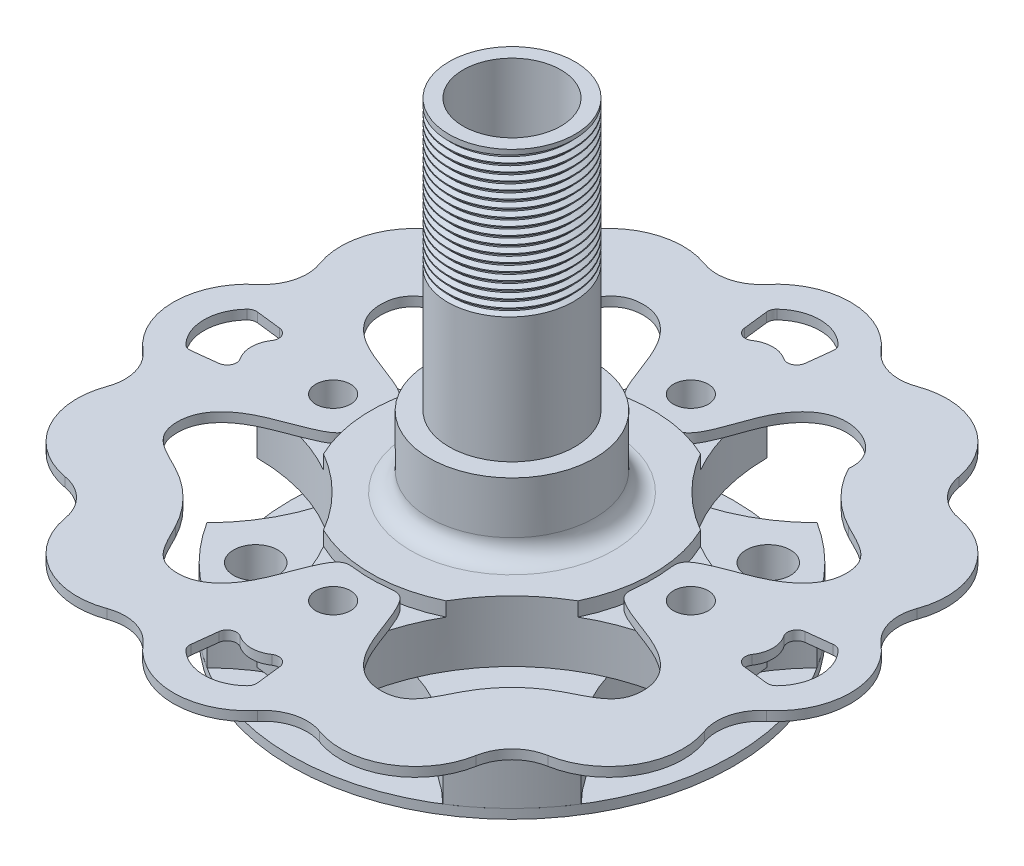
SolidWorks part; units mm, degrees
other "Camera1"
ref_plane "Front Plane" through (0, 0, 0) normal (0, 0, 1) x (1, 0, 0)
ref_plane "Top Plane" through (0, 0, 0) normal (0, 1, 0) x (1, 0, 0)
ref_plane "Right Plane" through (0, 0, 0) normal (1, 0, 0) x (0, 0, -1)
sketch "Sketch1" plane through (0, 0, 0) normal (0, 1, 0) x (1, 0, 0)
  line L0 (-91.3384, 0) -> (0, 0) construction
  line L1 (-79.1014, 45.6692) -> (0, 0) construction
  line L2 (-45.6692, 79.1014) -> (0, 0) construction
  line L3 (0, 91.3384) -> (0, 0) construction
  line L4 (-58.7488, 58.7488) -> (0, 0) construction
  line L5 (-77.6512, 8.9971) -> (-70.888, 8.2135)
  line L9 (0, 91.3384) -> (0, 0) construction
  line L10 (-8.9971, 77.6512) -> (-8.2135, 70.888)
  line L11 (8.9971, 77.6512) -> (8.2135, 70.888)
  line L12 (77.6512, 8.9971) -> (70.888, 8.2135)
  line L13 (0, 91.3384) -> (0, 0) construction
  line L16 (45.6692, 79.1014) -> (0, 0) construction
  line L17 (79.1014, 45.6692) -> (0, 0) construction
  line L18 (91.3384, 0) -> (0, 0) construction
  line L19 (58.7488, 58.7488) -> (0, 0) construction
  line L20 (91.3384, 0) -> (0, 0) construction
  line L23 (0, 91.3384) -> (0, 0) construction
  line L24 (77.6512, -8.9971) -> (70.888, -8.2135)
  line L25 (8.9971, -77.6512) -> (8.2135, -70.888)
  line L26 (-91.3384, 0) -> (0, 0) construction
  line L27 (91.3384, 0) -> (0, 0) construction
  line L28 (77.6512, -8.9971) -> (70.888, -8.2135) [skipped]
  line L30 (-8.9971, -77.6512) -> (-8.2135, -70.888) [skipped]
  line L32 (79.1014, -45.6692) -> (0, 0) construction
  line L33 (45.6692, -79.1014) -> (0, 0) construction
  line L34 (0, -91.3384) -> (0, 0) construction
  line L35 (58.7488, -58.7488) -> (0, 0) construction
  line L36 (0, -91.3384) -> (0, 0) construction
  line L37 (-45.6692, -79.1014) -> (0, 0) construction
  line L38 (-79.1014, -45.6692) -> (0, 0) construction
  line L39 (-58.7488, -58.7488) -> (0, 0) construction
  line L40 (8.9971, 77.6512) -> (8.2135, 70.888) [skipped]
  line L41 (45.6692, 79.1014) -> (0, 0) construction
  line L42 (79.1014, 45.6692) -> (0, 0) construction
  line L43 (58.7488, 58.7488) -> (0, 0) construction
  line L45 (91.3384, 0) -> (0, 0) construction
  line L46 (91.3384, 0) -> (0, 0) construction
  line L47 (79.1014, -45.6692) -> (0, 0) construction
  line L48 (45.6692, -79.1014) -> (0, 0) construction
  line L49 (0, -91.3384) -> (0, 0) construction
  line L50 (58.7488, -58.7488) -> (0, 0) construction
  line L51 (0, -91.3384) -> (0, 0) construction
  line L52 (91.3384, 0) -> (0, 0) construction
  line L53 (-8.9971, -77.6512) -> (-8.2135, -70.888)
  line L54 (-77.6512, -8.9971) -> (-70.888, -8.2135)
  line L55 (0, -91.3384) -> (0, 0) construction
  line L56 (-45.6692, -79.1014) -> (0, 0) construction
  line L57 (-79.1014, -45.6692) -> (0, 0) construction
  line L58 (-91.3384, 0) -> (0, 0) construction
  line L59 (-58.7488, -58.7488) -> (0, 0) construction
  line L60 (-91.3384, 0) -> (0, 0) construction
  line L61 (0, -91.3384) -> (0, 0) construction
  arc A0 (-83.0834, 0) -> (0, 83.0834) centre (0, 0) cw construction
  arc A2 (-91.3384, 0) -> (-84.1072, 15.4663) centre (-71.1829, 0) cw
  arc A3 (-84.1072, 15.4663) -> (-80.5721, 28.6594) centre (-91.7199, 24.5763) ccw
  arc A4 (-80.5721, 28.6594) -> (-65.1058, 55.4478) centre (-61.6462, 35.5915) cw
  arc A5 (-65.1058, 55.4478) -> (-55.4478, 65.1058) centre (-67.1436, 67.1436) ccw
  arc A6 (-55.4478, 65.1058) -> (-28.6594, 80.5721) centre (-35.5915, 61.6462) cw
  arc A7 (-28.6594, 80.5721) -> (-15.4663, 84.1072) centre (-24.5763, 91.7199) ccw
  arc A8 (-15.4663, 84.1072) -> (0, 91.3384) centre (0, 71.1829) cw
  arc A9 (-61.618, 35.4294) -> (-35.4294, 61.618) centre (-67.1436, 67.1436) ccw
  arc A10 (-38.1, 0) -> (-37.7962, 4.8015) centre (0, 0) cw
  arc A11 (-83.0834, 0) -> (-79.7781, 8.2307) centre (-71.1829, 0) cw
  arc A12 (-69.0761, 4.2678) -> (-70.3834, 0) centre (-62.7634, 0) ccw
  arc A14 (-83.0834, 0) -> (-78.8139, 9.1318) centre (-71.1829, 0) cw construction
  arc A15 (-77.6512, 8.9971) -> (-79.7781, 8.2307) centre (-77.9435, 6.474) ccw
  arc A16 (-69.0761, 4.2678) -> (-70.888, 8.2135) centre (-71.1804, 5.6904) ccw
  circle A17 centre (-48.26, 0) radius 4.699
  arc A29 (0, 38.1) -> (-4.8015, 37.7962) centre (0, 0) ccw
  arc A30 (-4.2678, 69.0761) -> (0, 70.3834) centre (0, 62.7634) cw
  arc A36 (-4.2678, 69.0761) -> (-8.2135, 70.888) centre (-5.6904, 71.1804) cw
  arc A41 (-8.9971, 77.6512) -> (-8.2307, 79.7781) centre (-6.474, 77.9435) cw
  arc A42 (0, 83.0834) -> (-8.2307, 79.7781) centre (0, 71.1829) ccw
  arc A50 (0, 91.3384) -> (15.4663, 84.1072) centre (0, 71.1829) cw
  arc A51 (15.4663, 84.1072) -> (28.6594, 80.5721) centre (24.5763, 91.7199) ccw
  arc A57 (28.6594, 80.5721) -> (55.4478, 65.1058) centre (35.5915, 61.6462) cw
  arc A62 (55.4478, 65.1058) -> (65.1058, 55.4478) centre (67.1436, 67.1436) ccw
  arc A63 (65.1058, 55.4478) -> (80.5721, 28.6594) centre (61.6462, 35.5915) cw
  arc A71 (80.5721, 28.6594) -> (84.1072, 15.4663) centre (91.7199, 24.5763) ccw
  arc A72 (84.1072, 15.4663) -> (91.3384, 0) centre (71.1829, 0) cw
  arc A78 (-38.1, 0) -> (-37.7962, -4.8015) centre (0, 0) ccw
  arc A81 (-69.0761, -4.2678) -> (-70.3834, 0) centre (-62.7634, 0) cw
  arc A83 (35.4294, 61.618) -> (61.618, 35.4294) centre (67.1436, 67.1436) ccw
  arc A84 (0, 38.1) -> (4.8015, 37.7962) centre (0, 0) cw
  arc A85 (91.3384, 0) -> (84.1072, -15.4663) centre (71.1829, 0) cw [skipped]
  arc A86 (84.1072, -15.4663) -> (80.5721, -28.6594) centre (91.7199, -24.5763) ccw [skipped]
  arc A87 (80.5721, -28.6594) -> (65.1058, -55.4478) centre (61.6462, -35.5915) cw [skipped]
  arc A88 (65.1058, -55.4478) -> (55.4478, -65.1058) centre (67.1436, -67.1436) ccw [skipped]
  arc A89 (55.4478, -65.1058) -> (28.6594, -80.5721) centre (35.5915, -61.6462) cw [skipped]
  arc A90 (28.6594, -80.5721) -> (15.4663, -84.1072) centre (24.5763, -91.7199) ccw [skipped]
  arc A91 (15.4663, -84.1072) -> (0, -91.3384) centre (0, -71.1829) cw [skipped]
  arc A92 (61.618, -35.4294) -> (35.4294, -61.618) centre (67.1436, -67.1436) ccw [skipped]
  arc A93 (83.0834, 0) -> (79.7781, -8.2307) centre (71.1829, 0) cw [skipped]
  arc A95 (77.6512, -8.9971) -> (79.7781, -8.2307) centre (77.9435, -6.474) ccw [skipped]
  arc A96 (69.0761, -4.2678) -> (70.888, -8.2135) centre (71.1804, -5.6904) ccw [skipped]
  arc A102 (0, -91.3384) -> (-15.4663, -84.1072) centre (0, -71.1829) cw [skipped]
  arc A103 (-15.4663, -84.1072) -> (-28.6594, -80.5721) centre (-24.5763, -91.7199) ccw [skipped]
  arc A104 (-28.6594, -80.5721) -> (-55.4478, -65.1058) centre (-35.5915, -61.6462) cw [skipped]
  arc A105 (-55.4478, -65.1058) -> (-65.1058, -55.4478) centre (-67.1436, -67.1436) ccw [skipped]
  arc A106 (-65.1058, -55.4478) -> (-80.5721, -28.6594) centre (-61.6462, -35.5915) cw [skipped]
  arc A107 (-80.5721, -28.6594) -> (-84.1072, -15.4663) centre (-91.7199, -24.5763) ccw [skipped]
  arc A108 (-84.1072, -15.4663) -> (-91.3384, 0) centre (-71.1829, 0) cw [skipped]
  arc A109 (-35.4294, -61.618) -> (-61.618, -35.4294) centre (-67.1436, -67.1436) ccw [skipped]
  arc A110 (0, -38.1) -> (-4.8015, -37.7962) centre (0, 0) cw [skipped]
  arc A111 (0, -83.0834) -> (-8.2307, -79.7781) centre (0, -71.1829) cw [skipped]
  arc A112 (-4.2678, -69.0761) -> (0, -70.3834) centre (0, -62.7634) ccw [skipped]
  arc A114 (-8.9971, -77.6512) -> (-8.2307, -79.7781) centre (-6.474, -77.9435) ccw [skipped]
  arc A115 (-4.2678, -69.0761) -> (-8.2135, -70.888) centre (-5.6904, -71.1804) ccw [skipped]
  arc A119 (83.0834, 0) -> (0, -83.0834) centre (0, 0) cw construction
  arc A121 (0, -83.0834) -> (-83.0834, 0) centre (0, 0) cw construction
  arc A123 (0, 91.3384) -> (15.4663, 84.1072) centre (0, 71.1829) cw [skipped]
  arc A124 (15.4663, 84.1072) -> (28.6594, 80.5721) centre (24.5763, 91.7199) ccw [skipped]
  arc A125 (28.6594, 80.5721) -> (55.4478, 65.1058) centre (35.5915, 61.6462) cw [skipped]
  arc A126 (55.4478, 65.1058) -> (65.1058, 55.4478) centre (67.1436, 67.1436) ccw [skipped]
  arc A127 (65.1058, 55.4478) -> (80.5721, 28.6594) centre (61.6462, 35.5915) cw [skipped]
  arc A128 (80.5721, 28.6594) -> (84.1072, 15.4663) centre (91.7199, 24.5763) ccw [skipped]
  arc A129 (84.1072, 15.4663) -> (91.3384, 0) centre (71.1829, 0) cw [skipped]
  arc A130 (35.4294, 61.618) -> (61.618, 35.4294) centre (67.1436, 67.1436) ccw [skipped]
  arc A131 (0, 38.1) -> (4.8015, 37.7962) centre (0, 0) cw [skipped]
  arc A132 (0, 83.0834) -> (8.2307, 79.7781) centre (0, 71.1829) cw [skipped]
  arc A133 (4.2678, 69.0761) -> (0, 70.3834) centre (0, 62.7634) ccw [skipped]
  arc A135 (8.9971, 77.6512) -> (8.2307, 79.7781) centre (6.474, 77.9435) ccw [skipped]
  arc A136 (4.2678, 69.0761) -> (8.2135, 70.888) centre (5.6904, 71.1804) ccw [skipped]
  arc A138 (0, 83.0834) -> (83.0834, 0) centre (0, 0) cw construction
  arc A144 (38.1, 0) -> (37.7962, -4.8015) centre (0, 0) cw [skipped]
  arc A145 (69.0761, -4.2678) -> (70.3834, 0) centre (62.7634, 0) ccw [skipped]
  arc A146 (0, 83.0834) -> (8.2307, 79.7781) centre (0, 71.1829) cw
  arc A147 (4.2678, 69.0761) -> (0, 70.3834) centre (0, 62.7634) ccw
  arc A148 (8.9971, 77.6512) -> (8.2307, 79.7781) centre (6.474, 77.9435) ccw
  arc A149 (4.2678, 69.0761) -> (8.2135, 70.888) centre (5.6904, 71.1804) ccw
  circle A150 centre (0, 48.26) radius 4.699
  arc A151 (38.1, 0) -> (37.7962, 4.8015) centre (0, 0) ccw
  arc A152 (69.0761, 4.2678) -> (70.3834, 0) centre (62.7634, 0) cw
  arc A153 (69.0761, 4.2678) -> (70.888, 8.2135) centre (71.1804, 5.6904) cw
  arc A154 (77.6512, 8.9971) -> (79.7781, 8.2307) centre (77.9435, 6.474) cw
  arc A155 (83.0834, 0) -> (79.7781, 8.2307) centre (71.1829, 0) ccw
  arc A156 (0, 38.1) -> (-4.8015, 37.7962) centre (0, 0) ccw
  arc A157 (-4.2678, 69.0761) -> (0, 70.3834) centre (0, 62.7634) cw
  arc A158 (0, 83.0834) -> (83.0834, 0) centre (0, 0) cw construction
  arc A159 (0, 91.3384) -> (91.3384, 0) centre (0, 0) cw construction
  arc A160 (91.3384, 0) -> (84.1072, -15.4663) centre (71.1829, 0) cw
  arc A161 (84.1072, -15.4663) -> (80.5721, -28.6594) centre (91.7199, -24.5763) ccw
  arc A162 (80.5721, -28.6594) -> (65.1058, -55.4478) centre (61.6462, -35.5915) cw
  arc A163 (65.1058, -55.4478) -> (55.4478, -65.1058) centre (67.1436, -67.1436) ccw
  arc A164 (55.4478, -65.1058) -> (28.6594, -80.5721) centre (35.5915, -61.6462) cw
  arc A165 (28.6594, -80.5721) -> (15.4663, -84.1072) centre (24.5763, -91.7199) ccw
  arc A166 (15.4663, -84.1072) -> (0, -91.3384) centre (0, -71.1829) cw
  arc A167 (61.618, -35.4294) -> (35.4294, -61.618) centre (67.1436, -67.1436) ccw
  arc A168 (38.1, 0) -> (37.7962, -4.8015) centre (0, 0) cw
  arc A169 (83.0834, 0) -> (79.7781, -8.2307) centre (71.1829, 0) cw
  arc A170 (69.0761, -4.2678) -> (70.3834, 0) centre (62.7634, 0) ccw
  arc A171 (77.6512, -8.9971) -> (79.7781, -8.2307) centre (77.9435, -6.474) ccw
  arc A172 (69.0761, -4.2678) -> (70.888, -8.2135) centre (71.1804, -5.6904) ccw
  circle A173 centre (48.26, 0) radius 4.699
  arc A174 (0, -38.1) -> (4.8015, -37.7962) centre (0, 0) ccw
  arc A175 (4.2678, -69.0761) -> (0, -70.3834) centre (0, -62.7634) cw
  arc A176 (4.2678, -69.0761) -> (8.2135, -70.888) centre (5.6904, -71.1804) cw
  arc A177 (8.9971, -77.6512) -> (8.2307, -79.7781) centre (6.474, -77.9435) cw
  arc A178 (0, -83.0834) -> (8.2307, -79.7781) centre (0, -71.1829) ccw
  arc A179 (38.1, 0) -> (37.7962, 4.8015) centre (0, 0) ccw
  arc A180 (69.0761, 4.2678) -> (70.3834, 0) centre (62.7634, 0) cw
  arc A181 (83.0834, 0) -> (0, -83.0834) centre (0, 0) cw construction
  arc A182 (91.3384, 0) -> (0, -91.3384) centre (0, 0) cw construction
  arc A183 (0, -91.3384) -> (-15.4663, -84.1072) centre (0, -71.1829) cw
  arc A184 (-15.4663, -84.1072) -> (-28.6594, -80.5721) centre (-24.5763, -91.7199) ccw
  arc A185 (-28.6594, -80.5721) -> (-55.4478, -65.1058) centre (-35.5915, -61.6462) cw
  arc A186 (-55.4478, -65.1058) -> (-65.1058, -55.4478) centre (-67.1436, -67.1436) ccw
  arc A187 (-65.1058, -55.4478) -> (-80.5721, -28.6594) centre (-61.6462, -35.5915) cw
  arc A188 (-80.5721, -28.6594) -> (-84.1072, -15.4663) centre (-91.7199, -24.5763) ccw
  arc A189 (-84.1072, -15.4663) -> (-91.3384, 0) centre (-71.1829, 0) cw
  arc A190 (-35.4294, -61.618) -> (-61.618, -35.4294) centre (-67.1436, -67.1436) ccw
  arc A191 (0, -38.1) -> (-4.8015, -37.7962) centre (0, 0) cw
  arc A192 (0, -83.0834) -> (-8.2307, -79.7781) centre (0, -71.1829) cw
  arc A193 (-4.2678, -69.0761) -> (0, -70.3834) centre (0, -62.7634) ccw
  arc A194 (-8.9971, -77.6512) -> (-8.2307, -79.7781) centre (-6.474, -77.9435) ccw
  arc A195 (-4.2678, -69.0761) -> (-8.2135, -70.888) centre (-5.6904, -71.1804) ccw
  circle A196 centre (0, -48.26) radius 4.699
  arc A197 (-38.1, 0) -> (-37.7962, -4.8015) centre (0, 0) ccw
  arc A198 (-69.0761, -4.2678) -> (-70.3834, 0) centre (-62.7634, 0) cw
  arc A199 (-69.0761, -4.2678) -> (-70.888, -8.2135) centre (-71.1804, -5.6904) cw
  arc A200 (-77.6512, -8.9971) -> (-79.7781, -8.2307) centre (-77.9435, -6.474) cw
  arc A201 (-83.0834, 0) -> (-79.7781, -8.2307) centre (-71.1829, 0) ccw
  arc A202 (0, -38.1) -> (4.8015, -37.7962) centre (0, 0) ccw
  arc A203 (4.2678, -69.0761) -> (0, -70.3834) centre (0, -62.7634) cw
  arc A204 (0, -83.0834) -> (-83.0834, 0) centre (0, 0) cw construction
  arc A205 (0, -91.3384) -> (-91.3384, 0) centre (0, 0) cw construction
  spline S0 degree 3 poles (-52.2384, 38.6101) (-57.1023, 36.0693) (-62.2546, 34.2055) (-63.3566, 23.0387) (-56.4818, 14.6017) (-38.7119, 10.4134) (-37.5569, 6.6856) (-37.7962, 4.8015) knots 0 0 0 0 0.284167 0.347787 0.6362 0.911955 1 1 1 1
  spline S1 degree 3 poles (-38.6101, 52.2384) (-36.0693, 57.1023) (-34.2055, 62.2546) (-23.0387, 63.3566) (-14.6017, 56.4818) (-10.4134, 38.7119) (-6.6856, 37.5569) (-4.8015, 37.7962) knots 0 0 0 0 0.284167 0.347787 0.6362 0.911955 1 1 1 1
  spline S2 degree 3 poles (38.6101, 52.2384) (39.4918, 58.7472) (27.2418, 66.5399) (13.0177, 55.4204) (10.7787, 36.3141) (4.8015, 37.7962) knots 0 0 0 0 0.347787 0.6362 1 1 1 1
  spline S3 degree 3 poles (52.2384, 38.6101) (57.1023, 36.0693) (62.2546, 34.2055) (63.3566, 23.0387) (56.4818, 14.6017) (38.7119, 10.4134) (37.5569, 6.6856) (37.7962, 4.8015) knots 0 0 0 0 0.284167 0.347787 0.6362 0.911955 1 1 1 1
  spline S4 degree 3 poles (52.2384, -38.6101) (57.1023, -36.0693) (62.2546, -34.2055) (63.3566, -23.0387) (56.4818, -14.6017) (38.7119, -10.4134) (37.5569, -6.6856) (37.7962, -4.8015) knots 0 0 0 0 0.284167 0.347787 0.6362 0.911955 1 1 1 1
  spline S5 degree 3 poles (38.6101, -52.2384) (36.0693, -57.1023) (34.2055, -62.2546) (23.0387, -63.3566) (14.6017, -56.4818) (10.4134, -38.7119) (6.6856, -37.5569) (4.8015, -37.7962) knots 0 0 0 0 0.284167 0.347787 0.6362 0.911955 1 1 1 1
  spline S6 degree 3 poles (-38.6101, -52.2384) (-36.0693, -57.1023) (-34.2055, -62.2546) (-23.0387, -63.3566) (-14.6017, -56.4818) (-10.4134, -38.7119) (-6.6856, -37.5569) (-4.8015, -37.7962) knots 0 0 0 0 0.284167 0.347787 0.6362 0.911955 1 1 1 1
  spline S7 degree 3 poles (-52.2384, -38.6101) (-57.1023, -36.0693) (-62.2546, -34.2055) (-63.3566, -23.0387) (-56.4818, -14.6017) (-38.7119, -10.4134) (-37.5569, -6.6856) (-37.7962, -4.8015) knots 0 0 0 0 0.284167 0.347787 0.6362 0.911955 1 1 1 1
  point P26 (0, 0)
  point P27 (-79.1014, 45.6692)
  point P32 (-45.6692, 79.1014)
  point P89 (0, 0)
  point P90 (0, 0)
  point P124 (0, 0)
  point P125 (0, 0)
  point P127 (0, 0)
  point P131 (0, 0)
  point P146 (0, 0)
  point P156 (0, 0)
  point P190 (0, 0)
  point P191 (0, 0)
  point P193 (0, 0)
  point P197 (0, 0)
  point P203 (0, 0)
  point P223 (0, 0)
  point P237 (0, 0)
  point P454 (0, 0)
  point P456 (0, 0)
  point P458 (0, 0)
  point P462 (0, 0)
  point P463 (0, 0)
  dimension "D5" = 10.16
  dimension "D8" = 7.62
  dimension "D11" = 2.54
  dimension "D12" = 2.54
  dimension "D3" = 9.398
  dimension "D7" = 4
  dimension "D4" = 20.32
  dimension "D6" = 8.255
  dimension "D13" = 4
extrude "Boss-Extrude2" add sketch "Sketch1" along normal blind 2.54 contours L10 A8 A7 A6 A5 A4 A3 A2 A11 A15 L5 A16 A12 A81 region at (-87.101, 0, -7.4424)
sketch "Sketch4" plane through (0, 0, 0) normal (0, -1, 0) x (1, 0, 0)
  line L0 (-58.858, 9.9314) -> (-58.858, -9.9314) construction
  line L1 (9.9314, 58.858) -> (-9.9314, 58.858) construction
  line L2 (58.858, -9.9314) -> (58.858, 9.9314) construction
  line L3 (-9.9314, -58.858) -> (9.9314, -58.858) construction
  line L4 (-9.9314, 58.858) -> (-58.858, 58.858) construction
  line L5 (-58.858, 58.858) -> (-58.858, 9.9314) construction
  circle A0 centre (0, 0) radius 59.69
  circle A1 centre (0, 0) radius 38.1 construction
  arc A2 (58.858, 9.9314) -> (9.9314, 58.858) centre (58.858, 58.858) cw
  arc A3 (9.9314, -58.858) -> (58.858, -9.9314) centre (58.858, -58.858) cw
  arc A5 (-9.9314, 58.858) -> (-58.858, 9.9314) centre (-58.858, 58.858) cw
  arc A6 (-58.858, -9.9314) -> (-9.9314, -58.858) centre (-58.858, -58.858) cw
  circle A15 centre (48.26, 0) radius 4.699 construction
  circle A16 centre (0, -48.26) radius 4.699 construction
  circle A17 centre (-48.26, 0) radius 4.699 construction
  circle A18 centre (0, 48.26) radius 4.699 construction
  circle A19 centre (48.26, 0) radius 4.699
  circle A20 centre (0, -48.26) radius 4.699
  circle A21 centre (-48.26, 0) radius 4.699
  circle A22 centre (0, 48.26) radius 4.699
  point P9 (-58.858, 0)
  point P12 (0, 58.858)
  point P19 (0, 0)
  point P31 (0, 0)
  dimension "D1" = 119.38
  dimension "D2" = 19.8628
  dimension "D4" = 90
  dimension "D3" = 4
  dimension "D5" = 4
extrude "Boss-Extrude3" add sketch "Sketch4" along normal blind 12.7 contours A0 A6 A3 A2 A5 A22 A21 A20 A19 region at (0, 0, 0)
sketch "Sketch5" plane through (0, -12.7, 0) normal (0, -1, 0) x (1, 0, 0)
  circle A4 centre (34.574, -34.574) radius 5.969
  circle A5 centre (34.574, 34.574) radius 5.969
  circle A6 centre (-34.574, 34.574) radius 5.969
  circle A7 centre (-34.574, -34.574) radius 5.969
  arc A16 (-50.5004, -31.8215) -> (-31.8215, -50.5004) centre (0, 0) ccw
  arc A17 (31.8215, -50.5004) -> (-31.8215, -50.5004) centre (0, -82.3219) ccw
  arc A18 (31.8215, -50.5004) -> (50.5004, -31.8215) centre (0, 0) ccw
  arc A19 (50.5004, 31.8215) -> (50.5004, -31.8215) centre (82.3219, 0) ccw
  arc A20 (50.5004, 31.8215) -> (31.8215, 50.5004) centre (0, 0) ccw
  arc A21 (-31.8215, 50.5004) -> (31.8215, 50.5004) centre (0, 82.3219) ccw
  arc A22 (-31.8215, 50.5004) -> (-50.5004, 31.8215) centre (0, 0) ccw
  arc A23 (-50.5004, -31.8215) -> (-50.5004, 31.8215) centre (-82.3219, 0) ccw
extrude "Boss-Extrude4" add sketch "Sketch5" along normal blind 15.24 separate body
sketch "Sketch6" plane through (0, -27.94, 0) normal (0, -1, 0) x (1, 0, 0)
  circle A0 centre (0, 0) radius 59.69
  circle A1 centre (0, 0) radius 25.4
  arc A2 (58.858, -9.9314) -> (58.858, 9.9314) centre (0, 0) ccw construction
  circle A3 centre (-34.574, -34.574) radius 5.969 construction
  circle A4 centre (34.574, -34.574) radius 5.969 construction
  circle A5 centre (34.574, 34.574) radius 5.969 construction
  circle A6 centre (-34.574, 34.574) radius 5.969 construction
  circle A7 centre (-34.574, -34.574) radius 5.969
  circle A8 centre (34.574, -34.574) radius 5.969
  circle A9 centre (34.574, 34.574) radius 5.969
  circle A10 centre (-34.574, 34.574) radius 5.969
  dimension "D1" = 50.8
extrude "Boss-Extrude5" add sketch "Sketch6" along normal blind 2.54 separate body
sketch "Sketch7" plane through (0, 0, 0) normal (0, 1, 0) x (1, 0, 0)
  circle A0 centre (0, 0) radius 38.1
  arc A1 (-37.7962, 4.8015) -> (-37.7962, -4.8015) centre (0, 0) ccw construction
  arc A11 (-45.2034, 11.8754) -> (-11.8754, 45.2034) centre (-58.858, 58.858) ccw
  arc A12 (-37.7962, 4.8015) -> (-37.7962, -4.8015) centre (0, 0) ccw
  arc A13 (-11.8754, -45.2034) -> (-45.2034, -11.8754) centre (-58.858, -58.858) ccw
  arc A15 (45.2034, -11.8754) -> (11.8754, -45.2034) centre (58.858, -58.858) ccw
  arc A17 (11.9707, 44.8798) -> (45.2034, 11.8754) centre (58.858, 58.858) ccw
  arc A19 (-34.3305, 16.5234) -> (-16.5234, 34.3305) centre (-58.858, 58.858) ccw
  arc A20 (-37.7962, 4.8015) -> (-37.7962, -4.8015) centre (0, 0) ccw
  arc A21 (-16.5234, -34.3305) -> (-34.3305, -16.5234) centre (-58.858, -58.858) ccw
  arc A23 (34.3305, -16.5234) -> (16.5234, -34.3305) centre (58.858, -58.858) ccw
  arc A25 (16.5234, 34.3305) -> (34.3305, 16.5234) centre (58.858, 58.858) ccw
  arc A26 (4.8015, 37.7962) -> (-4.8015, 37.7962) centre (0, 0) ccw
  arc A27 (4.8015, 37.7962) -> (-4.8015, 37.7962) centre (0, 0) ccw
  arc A28 (-4.8015, -37.7962) -> (4.8015, -37.7962) centre (0, 0) ccw
  arc A29 (-4.8015, -37.7962) -> (4.8015, -37.7962) centre (0, 0) ccw
  arc A30 (37.7962, -4.8015) -> (37.7962, 4.8015) centre (0, 0) ccw
  arc A31 (37.7962, -4.8015) -> (37.7962, 4.8015) centre (0, 0) ccw
  spline S8 degree 3 poles (2976.9947, 358.0163) (33.5756, 126.9835) (-48.0553, -146.4387) (2.9292, 414.707) (-862.0018, -2830.3277) knots -0.437178 -0.437178 -0.437178 -0.437178 0.862417 3.114377 3.114377 3.114377 3.114377 only from (-4.8015, 37.7962) to (-11.8754, 45.2034)
  spline S9 degree 3 poles (900.8755, 335.8111) (-245.803, 10.7239) (51.6226, 30.7541) (-75.4367, -16.6676) (-179.4615, -985.0902) knots -0.726756 -0.726756 -0.726756 -0.726756 0.911955 1.806148 1.806148 1.806148 1.806148 only from (-45.2034, 11.8754) to (-37.7962, 4.8015)
  spline S10 degree 3 poles (-4.8015, 37.7962) (-6.6856, 37.5569) (-8.9976, 38.2732) (-10.7743, 42.3579) (-11.8754, 45.2034) knots 0.774372 0.774372 0.774372 0.774372 0.862417 1 1 1 1
  spline S11 degree 3 poles (-358.0163, 2976.9947) (-126.9835, 33.5756) (146.4387, -48.0553) (-414.707, 2.9292) (2830.3277, -862.0018) knots -0.437178 -0.437178 -0.437178 -0.437178 0.862417 3.114377 3.114377 3.114377 3.114377 only from (-37.7962, -4.8015) to (-45.2034, -11.8754)
  spline S12 degree 3 poles (-37.7962, -4.8015) (-37.5569, -6.6856) (-38.2732, -8.9976) (-42.3579, -10.7743) (-45.2034, -11.8754) knots 0.774372 0.774372 0.774372 0.774372 0.862417 1 1 1 1
  spline S13 degree 3 poles (-862.0004, 2830.3225) (2.9291, -414.7066) (-48.055, 146.4363) (33.5749, -126.9812) (2976.8937, -358.0084) knots -1.340004 -1.340004 -1.340004 -1.340004 0.911955 2.211535 2.211535 2.211535 2.211535 only from (-11.8754, -45.2034) to (-4.8015, -37.7962)
  spline S14 degree 3 poles (-11.8754, -45.2034) (-10.7743, -42.3579) (-8.9976, -38.2732) (-6.6856, -37.5569) (-4.8015, -37.7962) knots 0.774372 0.774372 0.774372 0.774372 0.911955 1 1 1 1
  spline S15 degree 3 poles (-2976.9947, -358.0163) (-33.5756, -126.9835) (48.0553, 146.4387) (-2.9292, -414.707) (862.0018, 2830.3277) knots -0.437178 -0.437178 -0.437178 -0.437178 0.862417 3.114377 3.114377 3.114377 3.114377 only from (4.8015, -37.7962) to (11.8754, -45.2034)
  spline S16 degree 3 poles (4.8015, -37.7962) (6.6856, -37.5569) (8.9976, -38.2732) (10.7743, -42.3579) (11.8754, -45.2034) knots 0.774372 0.774372 0.774372 0.774372 0.862417 1 1 1 1
  spline S17 degree 3 poles (-2830.3225, -862.0004) (414.7066, 2.9291) (-146.4363, -48.055) (126.9812, 33.5749) (358.0084, 2976.8937) knots -1.340004 -1.340004 -1.340004 -1.340004 0.911955 2.211535 2.211535 2.211535 2.211535 only from (45.2034, -11.8754) to (37.7962, -4.8015)
  spline S18 degree 3 poles (45.2034, -11.8754) (42.3579, -10.7743) (38.2732, -8.9976) (37.5569, -6.6856) (37.7962, -4.8015) knots 0.774372 0.774372 0.774372 0.774372 0.911955 1 1 1 1
  spline S19 degree 3 poles (358.0163, -2976.9947) (126.9835, -33.5756) (-146.4387, 48.0553) (414.707, -2.9292) (-2830.3277, 862.0018) knots -0.437178 -0.437178 -0.437178 -0.437178 0.862417 3.114377 3.114377 3.114377 3.114377 only from (37.7962, 4.8015) to (45.2034, 11.8754)
  spline S20 degree 3 poles (37.7962, 4.8015) (37.5569, 6.6856) (38.2732, 8.9976) (42.3579, 10.7743) (45.2034, 11.8754) knots 0.774372 0.774372 0.774372 0.774372 0.862417 1 1 1 1
  spline S21 degree 3 poles (1348.0294, -2639.3043) (-1227.4206, 2924.7866) (1222.4599, -2840.1968) (-1227.3035, 2772.6078) knots -1.32616 -1.32616 -1.32616 -1.32616 2.776909 2.776909 2.776909 2.776909 only from (11.9707, 44.8798) to (4.8015, 37.7962)
  spline S22 degree 3 poles (11.9707, 44.8798) (10.2888, 40.4191) (8.4039, 36.903) (4.8015, 37.7962) knots 0.780744 0.780744 0.780744 0.780744 1 1 1 1
  arc M20 (-11.8754, 45.2034) -> (-45.2034, 11.8754) centre (-58.858, 58.858) cw
  arc M22 (-37.7962, 4.8015) -> (-37.7962, -4.8015) centre (0, 0) ccw
  arc M24 (-45.2034, -11.8754) -> (-11.8754, -45.2034) centre (-58.858, -58.858) cw
  arc M28 (11.8754, -45.2034) -> (45.2034, -11.8754) centre (58.858, -58.858) cw
  arc M32 (45.2034, 11.8754) -> (11.9707, 44.8798) centre (58.858, 58.858) cw
  dimension "D1" = 0
extrude "Boss-Extrude7" add sketch "Sketch7" along normal blind 3.81 contours A0 M28 M32 M20 M22 M24 region at (0, 0, 0.0002)
sketch "Sketch8" plane through (0, 3.81, 0) normal (0, 1, 0) x (1, 0, 0)
  circle A0 centre (0, 0) radius 22.3012
  dimension "D1" = 44.6024
extrude "Boss-Extrude8" add sketch "Sketch8" along normal blind 19.05
sketch "Sketch9" plane through (0, 22.86, 0) normal (0, 1, 0) x (1, 0, 0)
  circle A0 centre (0, 0) radius 16.9926
  dimension "D1" = 33.9852
extrude "Boss-Extrude9" add sketch "Sketch9" along normal blind 73.025 separate body
sketch "Sketch10" plane through (0, 95.885, 0) normal (0, 1, 0) x (1, 0, 0)
  circle A2 centre (0, 0) radius 13.1826
  circle A3 centre (0, 0) radius 13.1826
  dimension "D1" = 3.81
extrude "Cut-Extrude1" cut sketch "Sketch10" against normal through all both and the other way through all
thread "Thread1" pitch 2.1167 method cut profile "Thread Profile1" start angle 0, offset 0, length 38.1, pitch 2.1167, diameter 33.9852
ref_plane "Plane1" through (-16.9926, 95.885, 0) normal (0, 0, 1) x (-1, 0, 0)
sketch "Thread Profile1" plane through (-16.9926, 95.885, 0) normal (0, 0, 1) x (-1, 0, 0)
  line L0 (0, 0) -> (0, 2.1167) construction
  line L11 (0, 0) -> (0, 1.8521)
  line L12 (0, 1.8521) -> (-1.1457, 1.1906)
  line L13 (-1.1457, 1.1906) -> (-1.1457, 0.6615)
  line L15 (-1.1457, 0.6615) -> (0, 0)
  line L17 (-1.1457, 0.926) -> (0, 0.926) construction
  point P2 (0, 0)
  dimension "Pitch" = 2.1167
  dimension "Profile_Angle" = 60
  dimension "Profile_Land" = 0.5292
  dimension "Profile_Height" = 1.1457
fillet "Fillet2" radius 5.08 1 edges at (0, 3.81, 22.3012)
move or copy body "Body-Move/Copy1" [suppressed] bodies to move or copy 105 110 111 112
